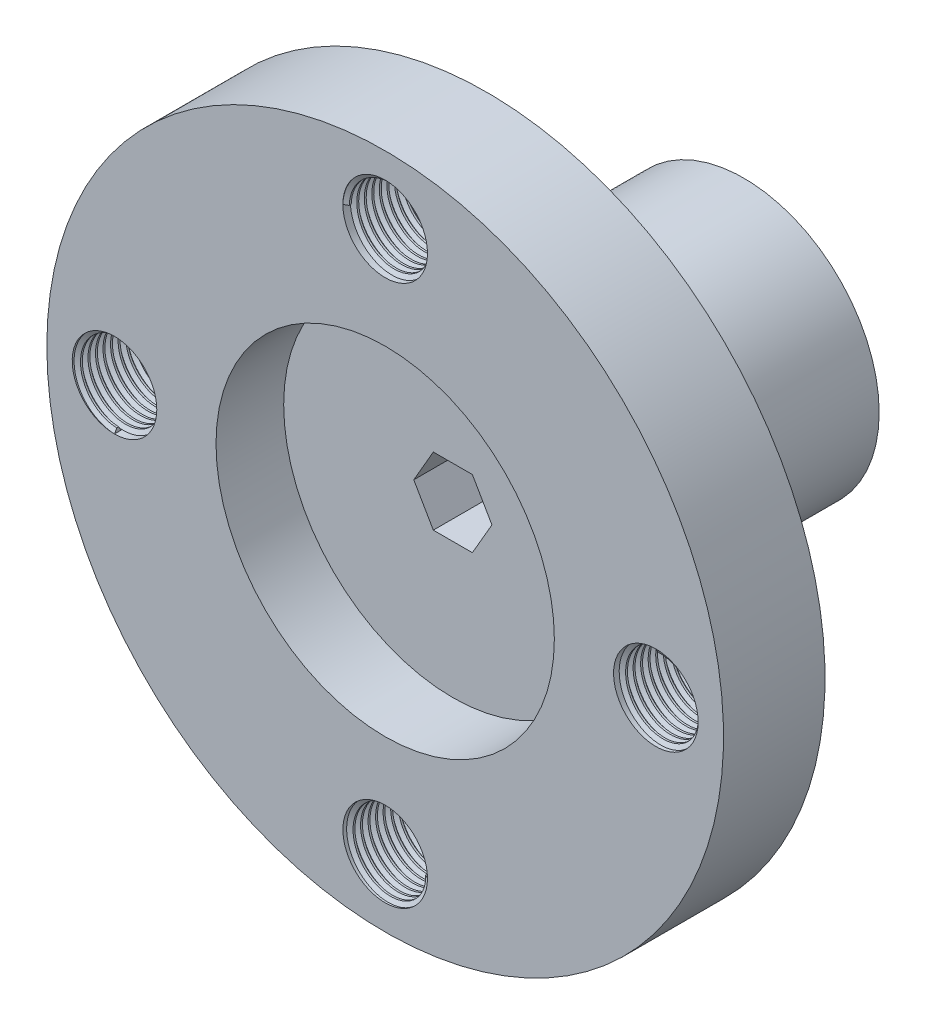
SolidWorks part; units mm, degrees
material "Plain Carbon Steel"
ref_plane "Front Plane" through (0, 0, 0) normal (0, 0, 1) x (1, 0, 0)
ref_plane "Top Plane" through (0, 0, 0) normal (0, 1, 0) x (1, 0, 0)
ref_plane "Right Plane" through (0, 0, 0) normal (1, 0, 0) x (0, 0, -1)
sketch "Sketch1" plane through (0, 0, 0) normal (0, 0, 1) x (1, 0, 0)
  circle A0 centre (0, 0) radius 25.4
  dimension "D1" = 50.8
extrude "Boss-Extrude1" add sketch "Sketch1" along normal blind 41.91
sketch "Sketch2" plane through (0, 0, 41.91) normal (0, 0, 1) x (1, 0, 0)
  circle A0 centre (0, 0) radius 38.1
  dimension "D1" = 76.2
extrude "Boss-Extrude2" add sketch "Sketch2" along normal blind 6.35
sketch "Sketch3" plane through (0, 0, 48.26) normal (0, 0, 1) x (1, 0, 0)
  circle A0 centre (0, 0) radius 63.5
  dimension "D1" = 127
extrude "Boss-Extrude3" add sketch "Sketch3" along normal blind 19.05
sketch "Sketch4" plane through (0, 0, 67.31) normal (0, 0, 1) x (1, 0, 0)
  circle A0 centre (0, 0) radius 31.75
  dimension "D1" = 63.5
extrude "Cut-Extrude1" cut sketch "Sketch4" against normal blind 12.7
sketch "Sketch5" plane through (0, 0, 54.61) normal (0, 0, 1) x (1, 0, 0)
  line L0 (55, 0) -> (-55, 0) construction
  line L1 (7.3323, 0) -> (3.6662, 6.35)
  line L2 (3.6662, 6.35) -> (-3.6662, 6.35)
  line L3 (-3.6662, 6.35) -> (-7.3323, 0)
  line L4 (-7.3323, 0) -> (-3.6662, -6.35)
  line L5 (-3.6662, -6.35) -> (3.6662, -6.35)
  line L6 (3.6662, -6.35) -> (7.3323, 0)
  circle A0 centre (0, 0) radius 6.35 construction
  point P1 (0, 0)
  dimension "D1" = 12.7
extrude "Cut-Extrude2" cut sketch "Sketch5" against normal through all both and the other way through all
sketch "Sketch6" plane through (0, 0, 67.31) normal (0, 0, 1) x (1, 0, 0)
  circle A0 centre (0, 50.8) radius 7.9375
  circle A1 centre (50.8, 0) radius 7.9375
  circle A2 centre (0, -50.8) radius 7.9375
  circle A3 centre (-50.8, 0) radius 7.9375
  circle A4 centre (0, 0) radius 63.5 construction
  point P11 (0, 0)
  dimension "D1" = 15.875
  dimension "D3" = 50.8
  dimension "D2" = 4
extrude "Cut-Extrude3" cut sketch "Sketch6" against normal up to next
ref_axis "Axis1" through (0, 0, 41.91) along (0, 0, -1)
ref_axis "Axis2" through (0, 50.8, 48.26) along (0, 0, 1)
ref_plane "Plane1" through (25.4, 0, 0) normal (1, 0, 0) x (0, 0, -1)
ref_axis "Axis3" through (0, -50.8, 48.26) along (0, 0, 1)
thread "Thread2" pitch 1.4111 method extrude profile "Thread Profile2" start angle 0, offset 0, length 0, pitch 1.4111, diameter 15.875
ref_plane "Plane3" through (-7.9375, 50.8, 67.31) normal (0, -1, 0) x (-1, 0, 0)
sketch "Thread Profile2" plane through (-7.9375, 50.8, 67.31) normal (0, -1, 0) x (-1, 0, 0)
  line L0 (0, 0) -> (0, 1.4111) construction
  line L11 (0, 0) -> (0, 1.2347)
  line L12 (0, 1.2347) -> (-0.7638, 0.7937)
  line L13 (-0.7638, 0.7937) -> (-0.7638, 0.441)
  line L15 (-0.7638, 0.441) -> (0, 0)
  line L17 (-0.7638, 0.6174) -> (0, 0.6174) construction
  point P2 (0, 0)
  dimension "Pitch" = 1.4111
  dimension "Profile_Angle" = 60
  dimension "Profile_Land" = 0.3528
  dimension "Profile_Height" = 0.7638
pattern_circular "CirPattern1" count 4 over 360 about axis through (0, 0, 67.31) along (0, 0, 1) of "Thread2"
